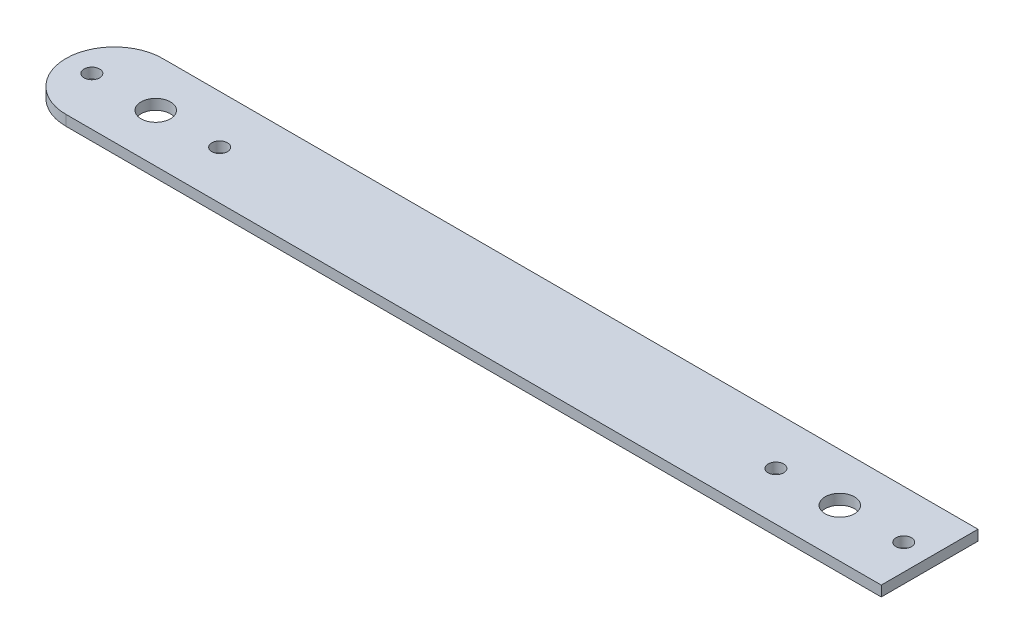
SolidWorks part; units mm, degrees
ref_plane "前视" through (0, 0, 0) normal (0, 0, 1) x (1, 0, 0)
ref_plane "上视" through (0, 0, 0) normal (0, 1, 0) x (1, 0, 0)
ref_plane "右视" through (0, 0, 0) normal (1, 0, 0) x (0, 0, -1)
sketch "草图1" plane through (0, 0, 0) normal (0, 1, 0) x (1, 0, 0)
  line L1 (-125, 14) -> (125, 14)
  line L2 (-125, 14) -> (-125, -14)
  line L3 (-125, -14) -> (125, -14)
  line L4 (125, 14) -> (125, -14)
  line L5 (-125, 14) -> (125, -14) construction
  line L6 (-125, -14) -> (125, 14) construction
  point P0 (0, 0)
  dimension "D1" = 250
  dimension "D2" = 28
extrude "凸台-拉伸1" add sketch "草图1" along normal blind 3 contours L2 | L2 | L3 L1 | L4 | L4 region at (0, 0, 0)
sketch "草图2" plane through (0, 3, 0) normal (0, 1, 0) x (1, 0, 0)
  circle A0 centre (-99, 0) radius 4.25
  circle A1 centre (99, 0) radius 4.25
  circle A2 centre (-33, 0) radius 4.25 construction
  circle A3 centre (33, 0) radius 4.25 construction
  dimension "D1" = 8.5
  dimension "D2" = 8.5
  dimension "D5" = 8.5
  dimension "D4" = 8.5
  dimension "D3" = 198
  dimension "D6" = 66
  dimension "D7" = 33
  dimension "D8" = 33
extrude "切除-拉伸1" cut sketch "草图2" against normal up to next
sketch "草图3" plane through (0, 3, 0) normal (0, 1, 0) x (1, 0, 0)
  circle A0 centre (-117.5, 0) radius 2.25
  circle A1 centre (-80.5, 0) radius 2.25
  circle A2 centre (80.5, 0) radius 2.25
  circle A3 centre (117.5, 0) radius 2.25
  circle A4 centre (-99, 0) radius 4.25 construction
  circle A5 centre (99, 0) radius 4.25 construction
  dimension "D2" = 18.5
  dimension "D3" = 4.5
  dimension "D4" = 4.5
  dimension "D6" = 18.5
  dimension "D7" = 4.5
  dimension "D8" = 4.5
  dimension "D1" = 37
  dimension "D5" = 37
extrude "切除-拉伸2" cut sketch "草图3" against normal up to next
sketch "草图4" plane through (0, 0, 0) normal (0, -1, 0) x (-1, 0, 0)
  circle A0 centre (66, 0) radius 4.25
  circle A1 centre (0, 0) radius 4.25
  circle A2 centre (-66, 0) radius 4.25
  dimension "D1" = 8.5
  dimension "D2" = 8.5
  dimension "D3" = 8.5
  dimension "D4" = 66
  dimension "D5" = 66
extrude "切除-拉伸3" [suppressed] cut sketch "草图4" against normal up to next
fillet "圆角1" 2 edges at (-125, 1.5, 14) (-125, 1.5, -14) type full round first side face at (0, 1.5, 14) second side face at (0, 1.5, -14) middle face at (-125, 1.5, 0)
